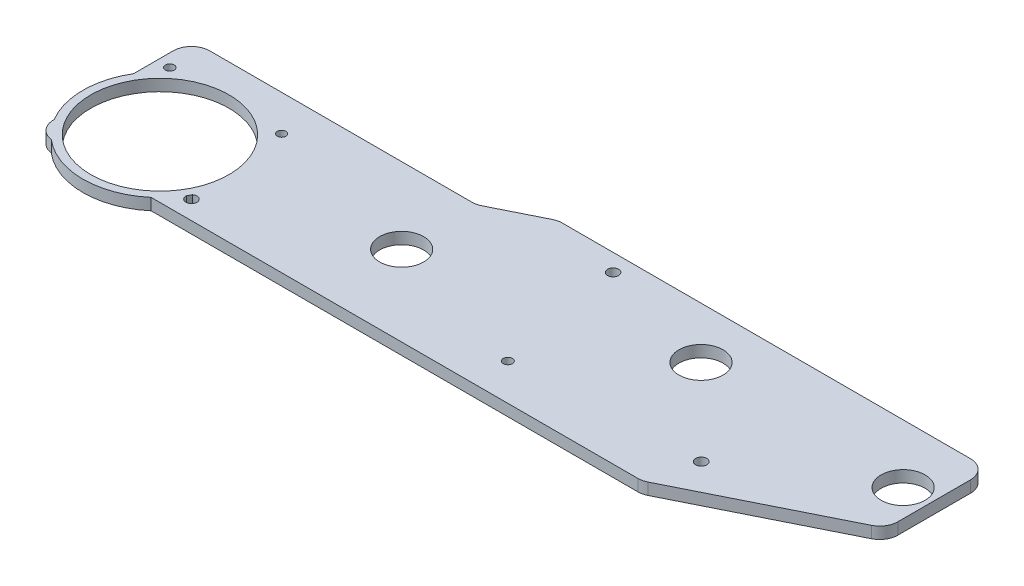
SolidWorks part; units mm, degrees
ref_plane "Front" through (0, 0, 0) normal (0, 0, 1) x (1, 0, 0)
ref_plane "Top" through (0, 0, 0) normal (0, 1, 0) x (1, 0, 0)
ref_plane "Right" through (0, 0, 0) normal (1, 0, 0) x (0, 0, -1)
sketch "Sketch1" plane through (0, 0, 0) normal (0, 1, 0) x (1, 0, 0)
  line L1 (0, 0) -> (210, 0)
  line L2 (0, 0) -> (0, -50)
  line L3 (0, -50) -> (210, -50)
  line L4 (210, 0) -> (210, -50)
  circle A7 centre (3.4895, -16.7877) radius 1.2117
  circle A8 centre (34.3726, -17.194) radius 1.1656
  circle A9 centre (37.5207, -44.9212) radius 1.5
  circle A10 centre (118.879, -40.0177) radius 1.25
  circle A11 centre (112.3021, -4.7393) radius 1.5
  circle A12 centre (168.9752, -37.4032) radius 1.5173
  dimension "D1" = 210
  dimension "D2" = 50
extrude "Boss-Extrude1" add sketch "Sketch1" along normal blind 3.175
sketch "Sketch2" plane through (0, 3.175, 0) normal (0, 1, 0) x (1, 0, 0)
  line L0 (210, 0) -> (0, 0) construction
  line L1 (0, 0) -> (0, -50) construction
  circle A0 centre (10, -26) radius 2
  circle A1 centre (10, -42) radius 2
  circle A2 centre (26, -26) radius 2
  circle A3 centre (26, -42) radius 2
  dimension "D1" = 16
  dimension "D2" = 16
  dimension "D3" = 16
  dimension "D4" = 26
  dimension "D5" = 10
  dimension "D6" = 10
  dimension "D7" = 26
  dimension "D8" = 16
extrude "Cut-Extrude1" cut sketch "Sketch2" against normal blind 10
sketch "Sketch3" plane through (0, 3.175, 0) normal (0, 1, 0) x (1, 0, 0)
  line L0 (210, 0) -> (0, 0) construction
  line L1 (210, 0) -> (0, 0) construction
  circle A0 centre (78.0103, -28.1) radius 6
  circle A1 centre (145.5313, -14) radius 6
  circle A2 centre (18, -34) radius 0.587
  circle A3 centre (26, -26) radius 2 construction
  circle A4 centre (202.6463, -16) radius 6
  dimension "D1" = 28.1
  dimension "D3" = 16
  dimension "D4" = 14
  dimension "D7" = 125.222
  dimension "D2" = 60.2996
  dimension "D5" = 8
  dimension "D6" = 8
  dimension "D8" = 57.15
extrude "Cut-Extrude2" cut sketch "Sketch3" against normal blind 57.15
sketch "Sketch4" [suppressed] plane through (0, 3.175, 0) normal (0, 1, 0) x (1, 0, 0)
  line L0 (3.4895, -16.7877) -> (18, -34)
  line L1 (3.4895, -20.6627) -> (5.9498, -23.5811)
  line L2 (18, -34) -> (34.3726, -17.194)
  line L3 (34.3726, -17.194) -> (75.8499, -28.1)
  line L4 (75.8499, -28.1) -> (37.5207, -44.9212)
  line L5 (7.3432, -17.194) -> (9.8664, -20.303)
  circle A0 centre (18, -34) radius 15.9299
  circle A1 centre (3.4895, -16.7877) radius 3.8751
  circle A2 centre (34.3726, -17.194) radius 3.7227
  circle A3 centre (37.5207, -44.9212) radius 3.8676
  circle A4 centre (75.8499, -28.1) radius 12.797
  circle A5 centre (112.3021, -4.7393) radius 5.1588
  circle A6 centre (118.879, -40.0177) radius 4.9035
  circle A7 centre (140.772, -16) radius 12.6375
  circle A8 centre (168.9752, -37.4032) radius 4.2066
  circle A9 centre (197.922, -16) radius 12.8
sketch "Sketch5" [suppressed] plane through (0, 3.175, 0) normal (0, 1, 0) x (1, 0, 0)
  line L0 (210, 0) -> (0, 0) construction
  line L2 (-0.6266, -16.7877) -> (37.5207, -16.7877)
  line L3 (-0.6266, -16.7877) -> (-0.6266, -44.9212)
  line L4 (-0.6266, -44.9212) -> (37.5207, -44.9212)
  line L5 (37.5207, -16.7877) -> (37.5207, -44.9212)
  line L6 (75.8499, -15.182) -> (37.5207, -15.182)
  line L7 (75.8499, -15.182) -> (75.8499, -44.9212)
  line L8 (75.8499, -44.9212) -> (37.5207, -44.9212)
  line L9 (37.5207, -15.182) -> (37.5207, -44.9212)
  line L10 (112.3021, -4.7393) -> (75.8499, -4.7393)
  line L11 (112.3021, -4.7393) -> (112.3021, -44.9212)
  line L12 (112.3021, -44.9212) -> (75.8499, -44.9212)
  line L13 (75.8499, -4.7393) -> (75.8499, -44.9212)
  line L14 (112.3021, -4.7393) -> (102.3945, -4.7393)
  line L16 (112.3021, -4.7393) -> (112.3021, 0)
  line L17 (112.3021, 0) -> (102.3945, 0)
  line L18 (102.3945, -4.7393) -> (102.3945, 0)
  line L19 (210, -50) -> (210, 0) construction
  line L20 (112.3021, -4.7393) -> (123.1553, -4.7393)
  line L21 (112.3021, -4.7393) -> (112.3021, 0)
  line L22 (112.3021, 0) -> (123.1553, 0)
  line L23 (123.1553, -4.7393) -> (123.1553, 0)
  line L24 (112.3021, -4.7393) -> (140.772, -4.7393)
  line L25 (112.3021, -4.7393) -> (112.3021, -40.0177)
  line L26 (112.3021, -40.0177) -> (140.772, -40.0177)
  line L27 (140.772, -4.7393) -> (140.772, -40.0177)
  line L28 (140.772, -16) -> (168.9752, -16)
  line L29 (140.772, -16) -> (140.772, -40.0177)
  line L30 (140.772, -40.0177) -> (168.9752, -40.0177)
  line L31 (168.9752, -16) -> (168.9752, -40.0177)
  line L32 (168.9752, -4.7393) -> (210, -4.7393)
  line L33 (168.9752, -4.7393) -> (168.9752, -40.0177)
  line L34 (168.9752, -40.0177) -> (210, -40.0177)
  line L35 (210, -4.7393) -> (210, -40.0177)
  line L36 (0, -50) -> (210, -50) construction
  line L37 (160.7629, -40.0177) -> (177.2091, -40.0177)
  line L38 (160.7629, -40.0177) -> (160.7629, -44.9212)
  line L39 (160.7629, -44.9212) -> (177.2091, -44.9212)
  line L40 (177.2091, -40.0177) -> (177.2091, -44.9212)
  line L41 (112.3021, -40.0177) -> (126.3591, -40.0177)
  line L42 (112.3021, -40.0177) -> (112.3021, -47.7828)
  line L43 (112.3021, -47.7828) -> (126.3591, -47.7828)
  line L44 (126.3591, -40.0177) -> (126.3591, -47.7828)
  line L45 (30.5963, -44.9212) -> (44.6115, -44.9212)
  line L46 (30.5963, -44.9212) -> (30.5963, -50)
  line L47 (30.5963, -50) -> (44.6115, -50)
  line L48 (44.6115, -44.9212) -> (44.6115, -50)
  line L50 (-0.6266, -44.9212) -> (30.5963, -44.9212)
  line L51 (-0.6266, -44.9212) -> (-0.6266, -50)
  line L52 (-0.6266, -50) -> (30.5963, -50)
  line L53 (30.5963, -44.9212) -> (30.5963, -50)
  circle A0 centre (3.4895, -16.7877) radius 4.1161
  circle A1 centre (34.3726, -17.194) radius 3.8132
  circle A2 centre (75.8499, -28.1) radius 12.918
  circle A3 centre (112.3021, -4.7393) radius 5.2663
  circle A4 centre (140.772, -16) radius 13.0245
  circle A5 centre (197.922, -16) radius 12.3805
  circle A6 centre (168.9752, -37.4032) radius 4.7643
  circle A7 centre (118.879, -40.0177) radius 5.279
  circle A8 centre (37.5207, -44.9212) radius 4.2049
  line M12 (0, 0) -> (0, -50)
  line M13 (0, -50) -> (210, -50)
  line M14 (210, -50) -> (210, 0)
  line M15 (210, 0) -> (0, 0)
extrude "Cut-Extrude5" [suppressed] cut sketch "Sketch5" against normal blind 11.52 contours A5 L32 L23 L24 A4 L28 L33 M14 M15 | A1 L6 L13 L10 L18 A0 L2 M15 M12 | L8 L48 L34 L40 L39 L38 L30 L26 L44 L43 L42 L12 M13 M14
fillet "Fillet1" [suppressed] radius 5
sketch "Sketch10" plane through (0, 3.175, 0) normal (0, 1, 0) x (1, 0, 0)
  line L0 (210, -27.8594) -> (165.5029, -50)
  line L1 (210, -50) -> (210, 0) construction
  line L2 (0, -50) -> (210, -50) construction
  line L3 (165.5029, -50) -> (210, -50)
  line L4 (210, -50) -> (210, -27.8594)
  line L5 (92.5326, 0) -> (77.6548, -7.4028)
  line L6 (210, 0) -> (0, 0) construction
  line L7 (77.6548, -7.4028) -> (0, -7.4028)
  line L8 (0, 0) -> (0, -50) construction
  line L9 (0, -7.4028) -> (0, 0)
  line L10 (0, 0) -> (92.5326, 0)
extrude "Cut-Extrude7" cut sketch "Sketch10" against normal blind 10
fillet "Fillet3" radius 5 7 edges at (0, 1.5875, 50) (0, 1.5875, 7.4028) (77.6548, 1.5875, 7.4028) (92.5326, 1.5875, 0) (210, 1.5875, 0) (210, 1.5875, 27.8594) (165.5029, 1.5875, 50)
sketch "Sketch11" plane through (0, 3.175, 0) normal (0, 1, 0) x (1, 0, 0)
  circle A0 centre (18, -34) radius 18.5
  circle A1 centre (10, -26) radius 2
  circle A2 centre (10, -42) radius 2
  circle A3 centre (26, -26) radius 2
  circle A4 centre (26, -42) radius 2
extrude "Boss-Extrude4" add sketch "Sketch11" against normal blind 3.175
sketch "Sketch12" plane through (0, 3.175, 0) normal (0, 1, 0) x (1, 0, 0)
  circle A0 centre (18, -34) radius 21
  circle A1 centre (10, -26) radius 2 construction
  circle A2 centre (10, -42) radius 2 construction
  point P6 (10, -42)
  dimension "D1" = 8
  dimension "D2" = 8
extrude "Boss-Extrude5" add sketch "Sketch12" against normal blind 3.175
sketch "Sketch13" plane through (0, 3.175, 0) normal (0, 1, 0) x (1, 0, 0)
  circle A0 centre (18, -34) radius 18.85
extrude "Cut-Extrude8" cut sketch "Sketch13" against normal blind 3.175
